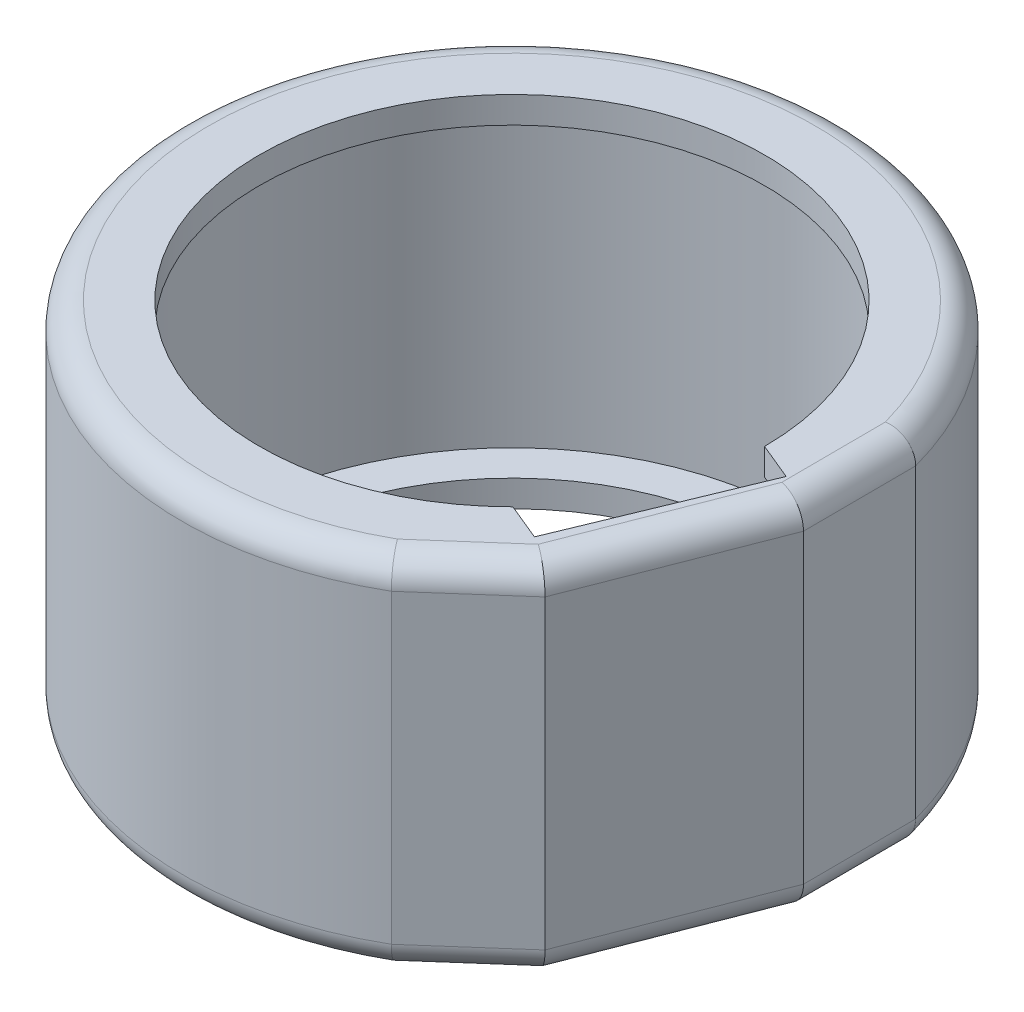
SolidWorks part; units mm, degrees
ref_plane "前视基准面" through (0, 0, 0) normal (0, 0, 1) x (1, 0, 0)
ref_plane "上视基准面" through (0, 0, 0) normal (0, 1, 0) x (1, 0, 0)
ref_plane "右视基准面" through (0, 0, 0) normal (1, 0, 0) x (0, 0, -1)
sketch "草图1" plane through (0, 0, 0) normal (0, 1, 0) x (1, 0, 0)
  line L0 (0, 0) -> (9.5, 0) construction
  line L1 (0, 0) -> (6.7336, -6.7014) construction
  line L6 (0, 0) -> (11.9775, 3.2094) construction
  line L7 (0, 0) -> (6.2, -10.7387) construction
  line L10 (9.5, 0) -> (11.9957, -1.0303) construction
  line L20 (11.9957, -1.0303) -> (9.276, -8.0328)
  line L21 (11.9957, -1.0303) -> (11.9775, 3.2094)
  line L22 (9.276, -8.0328) -> (6.2, -10.7387)
  line L23 (9.5, 0) -> (6.7336, -6.7014)
  arc A0 (9.5, 0) -> (6.7336, -6.7014) centre (0, 0) ccw
  arc A3 (11.9775, 3.2094) -> (6.2, -10.7387) centre (0, 0) ccw
  dimension "D1" = 2.7
  dimension "D2" = 12.4
  dimension "D3" = 9.5
extrude "凸台-拉伸1" add sketch "草图1" along normal blind 1
sketch "草图2" plane through (0, 0, 0) normal (0, -1, 0) x (-1, 0, 0)
  line L5 (0, 0) -> (-6.2, -10.7387) construction
  line L7 (0, 0) -> (-11.9775, 3.2094) construction
  line L9 (-8.0457, -7.3537) -> (-10.889, -0.4893)
  line L17 (-11.9957, -1.0303) -> (-11.9775, 3.2094)
  line L19 (-11.9957, -1.0303) -> (-9.276, -8.0328)
  line L20 (-9.276, -8.0328) -> (-6.2, -10.7387)
  arc A0 (-6.2, -10.7387) -> (-11.9775, 3.2094) centre (0, 0) ccw
  arc A1 (-8.0457, -7.3537) -> (-10.889, -0.4893) centre (0, 0) ccw
  dimension "D1" = 10.9
  dimension "D2" = 12.4
extrude "凸台-拉伸3" add sketch "草图2" along normal blind 11.5
sketch "草图5" plane through (0, -11.5, 0) normal (0, -1, 0) x (-1, 0, 0)
  line L4 (0, 0) -> (-6.2, -10.7387) construction
  line L5 (0, 0) -> (-11.9775, 3.2094) construction
  line L17 (-11.9775, 3.2094) -> (-11.9957, -1.0303)
  line L19 (-9.276, -8.0328) -> (-6.2, -10.7387)
  line L21 (-9.5, 0) -> (-6.7336, -6.7014) construction
  line L22 (-9.5, 0) -> (-6.7336, -6.7014)
  line L23 (-11.9957, -1.0303) -> (-9.276, -8.0328)
  arc A1 (-6.2, -10.7387) -> (-11.9775, 3.2094) centre (0, 0) ccw
  arc A2 (-6.7336, -6.7014) -> (-9.5, 0) centre (0, 0) ccw construction
  arc A3 (-6.7336, -6.7014) -> (-9.5, 0) centre (0, 0) ccw
extrude "凸台-拉伸4" add sketch "草图5" along normal blind 1
fillet "圆角1" radius 1 4 edges at (11.9866, -12.5, -1.0895) (-11.4561, -12.5, -4.7453) (7.738, -12.5, 9.3857) (10.6358, -12.5, 4.5315) type face fillet first side face at (11.9866, -5.75, -1.0895) first side face at (10.6358, -5.75, 4.5315) first side face at (7.738, -5.75, 9.3857) first side face at (-1.1837, -5.75, -0.4903) second side face at (4.7261, -12.5, 2.0206)
fillet "圆角2" radius 1 4 edges at (11.9866, 1, -1.0895) (-11.4561, 1, -4.7453) (7.738, 1, 9.3857) (10.6358, 1, 4.5315) type face fillet first side face at (11.9866, -5.25, -1.0895) first side face at (10.6358, -5.25, 4.5315) first side face at (7.738, -5.25, 9.3857) first side face at (-1.1837, -5.25, -0.4903) second side face at (-0.3322, 1, -0.1371)
sketch "草图7" plane through (8.1168, 0, 3.3507) normal (-0.9243, 0, -0.3816) x (-0.3816, 0, 0.9243)
  line L4 (-3.625, 1) -> (-3.625, 0) construction
  line L5 (-3.625, 1) -> (-3.625, 0)
  line L6 (-3.625, 1) -> (3.625, 1) construction
  line L7 (-3.625, 1) -> (3.625, 1)
  line L9 (-3.625, 0) -> (3.625, 0)
  line L10 (-3.625, 0) -> (-3.625, 1)
  line L11 (-3.625, 1) -> (3.625, 1)
  line L12 (3.625, 0) -> (3.625, 1)
extrude "切除-拉伸1" cut sketch "草图7" against normal blind 1.5 contours L9 L12 L7 L5
sketch3d "3DSketch2"
  spline S0 degree 1 poles (-10.2192, 1999.9934, 7.0234) (-10.2192, -2011.4808, 7.0234) knots -173.912465 -173.912465 174.91137 174.91137 only from (-10.2192, 0, 7.0234) to (-10.2192, -11.5, 7.0234) construction
  spline S1 degree 1 poles (-10.2192, 0, 7.0234) (-10.2192, -11.5, 7.0234) knots 0 0 1 1
sketch3d "3DSketch3"
  spline S0 degree 3 poles (6.2, -5.75, 10.7387) (-6.1793, -5.75, 17.8859) (-16.9263, -5.75, 8.461) (-11.4561, -5.75, -4.7453) (-5.9859, -5.75, -17.9515) (8.2778, -5.75, -17.0166) (11.9775, -5.75, -3.2094) knots 0 0 0 0 0.5 0.5 0.5 1 1 1 1 weights 1 0.547626 0.547626 1 0.547626 0.547626 1 construction
  spline S1 degree 3 poles (6.2, -5.75, 10.7387) (-6.1793, -5.75, 17.8859) (-16.9263, -5.75, 8.461) (-11.4561, -5.75, -4.7453) (-5.9859, -5.75, -17.9515) (8.2778, -5.75, -17.0166) (11.9775, -5.75, -3.2094) knots 0 0 0 0 0.5 0.5 0.5 1 1 1 1 weights 1 0.547626 0.547626 1 0.547626 0.547626 1
  spline S2 degree 1 poles (-10.2192, 0, 7.0234) (-10.2192, -11.5, 7.0234) knots 0 0 1 1 construction
  point P2 (-10.2192, -5.75, 7.0234)
ref_plane "Plane1" through (-10.2192, -5.75, 7.0234) normal (-0.8241, 0, 0.5664) x (0.5664, 0, 0.8241)
sketch "Sketch1" plane through (-10.2192, -5.75, 7.0234) normal (-0.8241, 0, 0.5664) x (0.5664, 0, 0.8241)
  circle A0 centre (0, 0) radius 0.8
extrude "Cut-Extrude1" cut sketch "Sketch1" against normal blind 10
